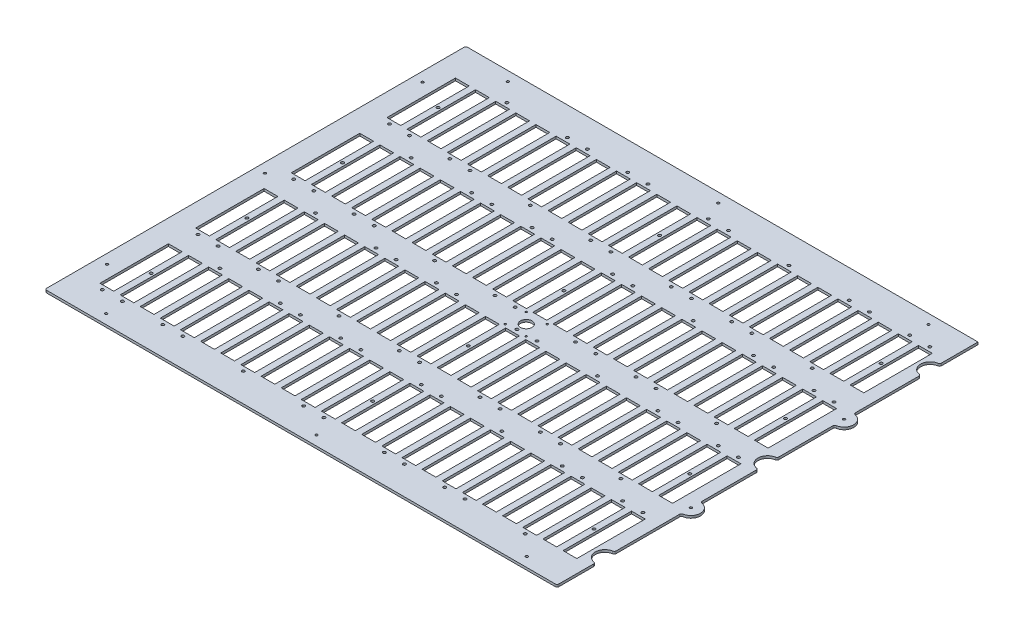
SolidWorks part; units mm, degrees
ref_plane "Front Plane" through (0, 0, 0) normal (0, 0, 1) x (1, 0, 0)
ref_plane "Top Plane" through (0, 0, 0) normal (0, 1, 0) x (1, 0, 0)
ref_plane "Right Plane" through (0, 0, 0) normal (1, 0, 0) x (0, 0, -1)
sketch "Sketch1" plane through (0, 0, 0) normal (0, 1, 0) x (1, 0, 0)
  line L0 (-340.1822, 0) -> (340.1822, 0) construction
  line L1 (-340.1822, -279.5524) -> (340.1822, -279.5524)
  line L2 (-340.1822, -279.5524) -> (-340.1822, 279.5524)
  line L3 (-340.1822, 279.5524) -> (340.1822, 279.5524)
  line L4 (340.1822, -279.5524) -> (340.1822, -228.7524)
  line L5 (-340.1822, -279.5524) -> (340.1822, 279.5524) construction
  line L6 (-340.1822, 279.5524) -> (340.1822, -279.5524) construction
  line L7 (340.1822, -89.0524) -> (340.1822, -12.7)
  line L8 (340.1822, -203.3524) -> (340.1822, -114.4524)
  line L9 (340.1822, 12.7) -> (340.1822, 89.0524)
  line L10 (340.1822, 114.4524) -> (340.1822, 203.3524)
  line L11 (340.1822, 228.7524) -> (340.1822, 279.5524)
  arc A0 (340.1822, 12.7) -> (340.1822, -12.7) centre (340.1822, 0) ccw
  arc A1 (340.1822, -114.4524) -> (340.1822, -89.0524) centre (340.1822, -101.7524) ccw
  arc A2 (340.1822, 89.0524) -> (340.1822, 114.4524) centre (340.1822, 101.7524) ccw
  arc A3 (340.1822, -203.3524) -> (340.1822, -228.7524) centre (340.1822, -216.0524) ccw
  arc A4 (340.1822, 228.7524) -> (340.1822, 203.3524) centre (340.1822, 216.0524) ccw
  point P0 (0, 0)
  dimension "D3" = 63.5
  dimension "D4" = 12.7
  dimension "D5" = 63.5
  dimension "D6" = 177.8
  dimension "D7" = 177.8
  dimension "D1" = 559.1048
  dimension "D2" = 680.3644
extrude "Boss-Extrude1" add sketch "Sketch1" along normal blind 3.175
sketch "Sketch17" plane through (0, 3.175, 0) normal (0, 1, 0) x (1, 0, 0)
  line L0 (340.1822, 279.5524) -> (-340.1822, 279.5524) construction
  line L1 (-314.7822, 254.1524) -> (327.4822, 254.1524) construction
  line L2 (-314.7822, 254.1524) -> (-314.7822, -254.1524) construction
  line L3 (-314.7822, -254.1524) -> (327.4822, -254.1524) construction
  line L4 (327.4822, 254.1524) -> (327.4822, -254.1524) construction
  line L5 (-340.1822, 279.5524) -> (-340.1822, -279.5524) construction
  line L6 (-340.1822, -279.5524) -> (340.1822, -279.5524) construction
  line L7 (340.1822, -203.3524) -> (340.1822, -114.4524) construction
  line L8 (-283.771, 236.1184) -> (-265.483, 236.1184)
  line L9 (-310.515, 236.1184) -> (-292.227, 236.1184)
  line L10 (-310.515, 236.1184) -> (-310.515, 145.1864)
  line L11 (-310.515, 145.1864) -> (-292.227, 145.1864)
  line L12 (-292.227, 236.1184) -> (-292.227, 145.1864)
  line L13 (-283.771, 236.1184) -> (-283.771, 145.1864)
  line L14 (-265.483, 236.1184) -> (-265.483, 145.1864)
  line L15 (-283.771, 145.1864) -> (-265.483, 145.1864)
  line L16 (-257.027, 236.1184) -> (-238.739, 236.1184)
  line L17 (-257.027, 236.1184) -> (-257.027, 145.1864)
  line L18 (-238.739, 236.1184) -> (-238.739, 145.1864)
  line L19 (-257.027, 145.1864) -> (-238.739, 145.1864)
  line L20 (-230.283, 236.1184) -> (-211.995, 236.1184)
  line L21 (-230.283, 236.1184) -> (-230.283, 145.1864)
  line L22 (-211.995, 236.1184) -> (-211.995, 145.1864)
  line L23 (-230.283, 145.1864) -> (-211.995, 145.1864)
  line L24 (-203.539, 236.1184) -> (-185.251, 236.1184)
  line L25 (-203.539, 236.1184) -> (-203.539, 145.1864)
  line L26 (-185.251, 236.1184) -> (-185.251, 145.1864)
  line L27 (-203.539, 145.1864) -> (-185.251, 145.1864)
  line L28 (-176.795, 236.1184) -> (-158.507, 236.1184)
  line L29 (-176.795, 236.1184) -> (-176.795, 145.1864)
  line L30 (-158.507, 236.1184) -> (-158.507, 145.1864)
  line L31 (-176.795, 145.1864) -> (-158.507, 145.1864)
  line L32 (-150.0511, 236.1184) -> (-131.7631, 236.1184)
  line L33 (-150.0511, 236.1184) -> (-150.0511, 145.1864)
  line L34 (-131.7631, 236.1184) -> (-131.7631, 145.1864)
  line L35 (-150.0511, 145.1864) -> (-131.7631, 145.1864)
  line L36 (-123.3071, 236.1184) -> (-105.0191, 236.1184)
  line L37 (-123.3071, 236.1184) -> (-123.3071, 145.1864)
  line L38 (-105.0191, 236.1184) -> (-105.0191, 145.1864)
  line L39 (-123.3071, 145.1864) -> (-105.0191, 145.1864)
  line L40 (-96.5631, 236.1184) -> (-78.2751, 236.1184)
  line L41 (-96.5631, 236.1184) -> (-96.5631, 145.1864)
  line L42 (-78.2751, 236.1184) -> (-78.2751, 145.1864)
  line L43 (-96.5631, 145.1864) -> (-78.2751, 145.1864)
  line L44 (-69.8191, 236.1184) -> (-51.5311, 236.1184)
  line L45 (-69.8191, 236.1184) -> (-69.8191, 145.1864)
  line L46 (-51.5311, 236.1184) -> (-51.5311, 145.1864)
  line L47 (-69.8191, 145.1864) -> (-51.5311, 145.1864)
  line L48 (-43.0751, 236.1184) -> (-24.7871, 236.1184)
  line L49 (-43.0751, 236.1184) -> (-43.0751, 145.1864)
  line L50 (-24.7871, 236.1184) -> (-24.7871, 145.1864)
  line L51 (-43.0751, 145.1864) -> (-24.7871, 145.1864)
  line L52 (-16.3311, 236.1184) -> (1.9569, 236.1184)
  line L53 (-16.3311, 236.1184) -> (-16.3311, 145.1864)
  line L54 (1.9569, 236.1184) -> (1.9569, 145.1864)
  line L55 (-16.3311, 145.1864) -> (1.9569, 145.1864)
  line L56 (10.4129, 236.1184) -> (28.7009, 236.1184)
  line L57 (10.4129, 236.1184) -> (10.4129, 145.1864)
  line L58 (28.7009, 236.1184) -> (28.7009, 145.1864)
  line L59 (10.4129, 145.1864) -> (28.7009, 145.1864)
  line L60 (37.1569, 236.1184) -> (55.4449, 236.1184)
  line L61 (37.1569, 236.1184) -> (37.1569, 145.1864)
  line L62 (55.4449, 236.1184) -> (55.4449, 145.1864)
  line L63 (37.1569, 145.1864) -> (55.4449, 145.1864)
  line L64 (63.9009, 236.1184) -> (82.1889, 236.1184)
  line L65 (63.9009, 236.1184) -> (63.9009, 145.1864)
  line L66 (82.1889, 236.1184) -> (82.1889, 145.1864)
  line L67 (63.9009, 145.1864) -> (82.1889, 145.1864)
  line L68 (90.6449, 236.1184) -> (108.9329, 236.1184)
  line L69 (90.6449, 236.1184) -> (90.6449, 145.1864)
  line L70 (108.9329, 236.1184) -> (108.9329, 145.1864)
  line L71 (90.6449, 145.1864) -> (108.9329, 145.1864)
  line L72 (117.3889, 236.1184) -> (135.6769, 236.1184)
  line L73 (117.3889, 236.1184) -> (117.3889, 145.1864)
  line L74 (135.6769, 236.1184) -> (135.6769, 145.1864)
  line L75 (117.3889, 145.1864) -> (135.6769, 145.1864)
  line L76 (144.1329, 236.1184) -> (162.4209, 236.1184)
  line L77 (144.1329, 236.1184) -> (144.1329, 145.1864)
  line L78 (162.4209, 236.1184) -> (162.4209, 145.1864)
  line L79 (144.1329, 145.1864) -> (162.4209, 145.1864)
  line L80 (170.8768, 236.1184) -> (189.1648, 236.1184)
  line L81 (170.8768, 236.1184) -> (170.8768, 145.1864)
  line L82 (189.1648, 236.1184) -> (189.1648, 145.1864)
  line L83 (170.8768, 145.1864) -> (189.1648, 145.1864)
  line L84 (197.6208, 236.1184) -> (215.9088, 236.1184)
  line L85 (197.6208, 236.1184) -> (197.6208, 145.1864)
  line L86 (215.9088, 236.1184) -> (215.9088, 145.1864)
  line L87 (197.6208, 145.1864) -> (215.9088, 145.1864)
  line L88 (224.3648, 236.1184) -> (242.6528, 236.1184)
  line L89 (224.3648, 236.1184) -> (224.3648, 145.1864)
  line L90 (242.6528, 236.1184) -> (242.6528, 145.1864)
  line L91 (224.3648, 145.1864) -> (242.6528, 145.1864)
  line L92 (251.1088, 236.1184) -> (269.3968, 236.1184)
  line L93 (251.1088, 236.1184) -> (251.1088, 145.1864)
  line L94 (269.3968, 236.1184) -> (269.3968, 145.1864)
  line L95 (251.1088, 145.1864) -> (269.3968, 145.1864)
  line L96 (277.8528, 236.1184) -> (296.1408, 236.1184)
  line L97 (277.8528, 236.1184) -> (277.8528, 145.1864)
  line L98 (296.1408, 236.1184) -> (296.1408, 145.1864)
  line L99 (277.8528, 145.1864) -> (296.1408, 145.1864)
  line L100 (304.5968, 236.1184) -> (322.8848, 236.1184)
  line L101 (304.5968, 236.1184) -> (304.5968, 145.1864)
  line L102 (322.8848, 236.1184) -> (322.8848, 145.1864)
  line L103 (304.5968, 145.1864) -> (322.8848, 145.1864)
  line L104 (-283.771, 109.0422) -> (-265.483, 109.0422)
  line L105 (-283.771, 109.0422) -> (-283.771, 18.1102)
  line L106 (-265.483, 109.0422) -> (-265.483, 18.1102)
  line L107 (-283.771, 18.1102) -> (-265.483, 18.1102)
  line L108 (-257.027, 109.0422) -> (-238.739, 109.0422)
  line L109 (-257.027, 109.0422) -> (-257.027, 18.1102)
  line L110 (-238.739, 109.0422) -> (-238.739, 18.1102)
  line L111 (-257.027, 18.1102) -> (-238.739, 18.1102)
  line L112 (-230.283, 109.0422) -> (-211.995, 109.0422)
  line L113 (-230.283, 109.0422) -> (-230.283, 18.1102)
  line L114 (-211.995, 109.0422) -> (-211.995, 18.1102)
  line L115 (-230.283, 18.1102) -> (-211.995, 18.1102)
  line L116 (-203.539, 109.0422) -> (-185.251, 109.0422)
  line L117 (-203.539, 109.0422) -> (-203.539, 18.1102)
  line L118 (-185.251, 109.0422) -> (-185.251, 18.1102)
  line L119 (-203.539, 18.1102) -> (-185.251, 18.1102)
  line L120 (-176.795, 109.0422) -> (-158.507, 109.0422)
  line L121 (-176.795, 109.0422) -> (-176.795, 18.1102)
  line L122 (-158.507, 109.0422) -> (-158.507, 18.1102)
  line L123 (-176.795, 18.1102) -> (-158.507, 18.1102)
  line L124 (-150.0511, 109.0422) -> (-131.7631, 109.0422)
  line L125 (-150.0511, 109.0422) -> (-150.0511, 18.1102)
  line L126 (-131.7631, 109.0422) -> (-131.7631, 18.1102)
  line L127 (-150.0511, 18.1102) -> (-131.7631, 18.1102)
  line L128 (-123.3071, 109.0422) -> (-105.0191, 109.0422)
  line L129 (-123.3071, 109.0422) -> (-123.3071, 18.1102)
  line L130 (-105.0191, 109.0422) -> (-105.0191, 18.1102)
  line L131 (-123.3071, 18.1102) -> (-105.0191, 18.1102)
  line L132 (-96.5631, 109.0422) -> (-78.2751, 109.0422)
  line L133 (-96.5631, 109.0422) -> (-96.5631, 18.1102)
  line L134 (-78.2751, 109.0422) -> (-78.2751, 18.1102)
  line L135 (-96.5631, 18.1102) -> (-78.2751, 18.1102)
  line L136 (-69.8191, 109.0422) -> (-51.5311, 109.0422)
  line L137 (-69.8191, 109.0422) -> (-69.8191, 18.1102)
  line L138 (-51.5311, 109.0422) -> (-51.5311, 18.1102)
  line L139 (-69.8191, 18.1102) -> (-51.5311, 18.1102)
  line L140 (-43.0751, 109.0422) -> (-24.7871, 109.0422)
  line L141 (-43.0751, 109.0422) -> (-43.0751, 18.1102)
  line L142 (-24.7871, 109.0422) -> (-24.7871, 18.1102)
  line L143 (-43.0751, 18.1102) -> (-24.7871, 18.1102)
  line L144 (-16.3311, 109.0422) -> (1.9569, 109.0422)
  line L145 (-16.3311, 109.0422) -> (-16.3311, 18.1102)
  line L146 (1.9569, 109.0422) -> (1.9569, 18.1102)
  line L147 (-16.3311, 18.1102) -> (1.9569, 18.1102)
  line L148 (10.4129, 109.0422) -> (28.7009, 109.0422)
  line L149 (10.4129, 109.0422) -> (10.4129, 18.1102)
  line L150 (28.7009, 109.0422) -> (28.7009, 18.1102)
  line L151 (10.4129, 18.1102) -> (28.7009, 18.1102)
  line L152 (37.1569, 109.0422) -> (55.4449, 109.0422)
  line L153 (37.1569, 109.0422) -> (37.1569, 18.1102)
  line L154 (55.4449, 109.0422) -> (55.4449, 18.1102)
  line L155 (37.1569, 18.1102) -> (55.4449, 18.1102)
  line L156 (63.9009, 109.0422) -> (82.1889, 109.0422)
  line L157 (63.9009, 109.0422) -> (63.9009, 18.1102)
  line L158 (82.1889, 109.0422) -> (82.1889, 18.1102)
  line L159 (63.9009, 18.1102) -> (82.1889, 18.1102)
  line L160 (90.6449, 109.0422) -> (108.9329, 109.0422)
  line L161 (90.6449, 109.0422) -> (90.6449, 18.1102)
  line L162 (108.9329, 109.0422) -> (108.9329, 18.1102)
  line L163 (90.6449, 18.1102) -> (108.9329, 18.1102)
  line L164 (117.3889, 109.0422) -> (135.6769, 109.0422)
  line L165 (117.3889, 109.0422) -> (117.3889, 18.1102)
  line L166 (135.6769, 109.0422) -> (135.6769, 18.1102)
  line L167 (117.3889, 18.1102) -> (135.6769, 18.1102)
  line L168 (144.1329, 109.0422) -> (162.4209, 109.0422)
  line L169 (144.1329, 109.0422) -> (144.1329, 18.1102)
  line L170 (162.4209, 109.0422) -> (162.4209, 18.1102)
  line L171 (144.1329, 18.1102) -> (162.4209, 18.1102)
  line L172 (170.8768, 109.0422) -> (189.1648, 109.0422)
  line L173 (170.8768, 109.0422) -> (170.8768, 18.1102)
  line L174 (189.1648, 109.0422) -> (189.1648, 18.1102)
  line L175 (170.8768, 18.1102) -> (189.1648, 18.1102)
  line L176 (197.6208, 109.0422) -> (215.9088, 109.0422)
  line L177 (197.6208, 109.0422) -> (197.6208, 18.1102)
  line L178 (215.9088, 109.0422) -> (215.9088, 18.1102)
  line L179 (197.6208, 18.1102) -> (215.9088, 18.1102)
  line L180 (224.3648, 109.0422) -> (242.6528, 109.0422)
  line L181 (224.3648, 109.0422) -> (224.3648, 18.1102)
  line L182 (242.6528, 109.0422) -> (242.6528, 18.1102)
  line L183 (224.3648, 18.1102) -> (242.6528, 18.1102)
  line L184 (251.1088, 109.0422) -> (269.3968, 109.0422)
  line L185 (251.1088, 109.0422) -> (251.1088, 18.1102)
  line L186 (269.3968, 109.0422) -> (269.3968, 18.1102)
  line L187 (251.1088, 18.1102) -> (269.3968, 18.1102)
  line L188 (277.8528, 109.0422) -> (296.1408, 109.0422)
  line L189 (277.8528, 109.0422) -> (277.8528, 18.1102)
  line L190 (296.1408, 109.0422) -> (296.1408, 18.1102)
  line L191 (277.8528, 18.1102) -> (296.1408, 18.1102)
  line L192 (304.5968, 109.0422) -> (322.8848, 109.0422)
  line L193 (304.5968, 109.0422) -> (304.5968, 18.1102)
  line L194 (322.8848, 109.0422) -> (322.8848, 18.1102)
  line L195 (304.5968, 18.1102) -> (322.8848, 18.1102)
  line L196 (-283.771, -18.034) -> (-265.483, -18.034)
  line L197 (-283.771, -18.034) -> (-283.771, -108.966)
  line L198 (-265.483, -18.034) -> (-265.483, -108.966)
  line L199 (-283.771, -108.966) -> (-265.483, -108.966)
  line L200 (-257.027, -18.034) -> (-238.739, -18.034)
  line L201 (-257.027, -18.034) -> (-257.027, -108.966)
  line L202 (-238.739, -18.034) -> (-238.739, -108.966)
  line L203 (-257.027, -108.966) -> (-238.739, -108.966)
  line L204 (-230.283, -18.034) -> (-211.995, -18.034)
  line L205 (-230.283, -18.034) -> (-230.283, -108.966)
  line L206 (-211.995, -18.034) -> (-211.995, -108.966)
  line L207 (-230.283, -108.966) -> (-211.995, -108.966)
  line L208 (-203.539, -18.034) -> (-185.251, -18.034)
  line L209 (-203.539, -18.034) -> (-203.539, -108.966)
  line L210 (-185.251, -18.034) -> (-185.251, -108.966)
  line L211 (-203.539, -108.966) -> (-185.251, -108.966)
  line L212 (-176.795, -18.034) -> (-158.507, -18.034)
  line L213 (-176.795, -18.034) -> (-176.795, -108.966)
  line L214 (-158.507, -18.034) -> (-158.507, -108.966)
  line L215 (-176.795, -108.966) -> (-158.507, -108.966)
  line L216 (-150.0511, -18.034) -> (-131.7631, -18.034)
  line L217 (-150.0511, -18.034) -> (-150.0511, -108.966)
  line L218 (-131.7631, -18.034) -> (-131.7631, -108.966)
  line L219 (-150.0511, -108.966) -> (-131.7631, -108.966)
  line L220 (-123.3071, -18.034) -> (-105.0191, -18.034)
  line L221 (-123.3071, -18.034) -> (-123.3071, -108.966)
  line L222 (-105.0191, -18.034) -> (-105.0191, -108.966)
  line L223 (-123.3071, -108.966) -> (-105.0191, -108.966)
  line L224 (-96.5631, -18.034) -> (-78.2751, -18.034)
  line L225 (-96.5631, -18.034) -> (-96.5631, -108.966)
  line L226 (-78.2751, -18.034) -> (-78.2751, -108.966)
  line L227 (-96.5631, -108.966) -> (-78.2751, -108.966)
  line L228 (-69.8191, -18.034) -> (-51.5311, -18.034)
  line L229 (-69.8191, -18.034) -> (-69.8191, -108.966)
  line L230 (-51.5311, -18.034) -> (-51.5311, -108.966)
  line L231 (-69.8191, -108.966) -> (-51.5311, -108.966)
  line L232 (-43.0751, -18.034) -> (-24.7871, -18.034)
  line L233 (-43.0751, -18.034) -> (-43.0751, -108.966)
  line L234 (-24.7871, -18.034) -> (-24.7871, -108.966)
  line L235 (-43.0751, -108.966) -> (-24.7871, -108.966)
  line L236 (-16.3311, -18.034) -> (1.9569, -18.034)
  line L237 (-16.3311, -18.034) -> (-16.3311, -108.966)
  line L238 (1.9569, -18.034) -> (1.9569, -108.966)
  line L239 (-16.3311, -108.966) -> (1.9569, -108.966)
  line L240 (10.4129, -18.034) -> (28.7009, -18.034)
  line L241 (10.4129, -18.034) -> (10.4129, -108.966)
  line L242 (28.7009, -18.034) -> (28.7009, -108.966)
  line L243 (10.4129, -108.966) -> (28.7009, -108.966)
  line L244 (37.1569, -18.034) -> (55.4449, -18.034)
  line L245 (37.1569, -18.034) -> (37.1569, -108.966)
  line L246 (55.4449, -18.034) -> (55.4449, -108.966)
  line L247 (37.1569, -108.966) -> (55.4449, -108.966)
  line L248 (63.9009, -18.034) -> (82.1889, -18.034)
  line L249 (63.9009, -18.034) -> (63.9009, -108.966)
  line L250 (82.1889, -18.034) -> (82.1889, -108.966)
  line L251 (63.9009, -108.966) -> (82.1889, -108.966)
  line L252 (90.6449, -18.034) -> (108.9329, -18.034)
  line L253 (90.6449, -18.034) -> (90.6449, -108.966)
  line L254 (108.9329, -18.034) -> (108.9329, -108.966)
  line L255 (90.6449, -108.966) -> (108.9329, -108.966)
  line L256 (117.3889, -18.034) -> (135.6769, -18.034)
  line L257 (117.3889, -18.034) -> (117.3889, -108.966)
  line L258 (135.6769, -18.034) -> (135.6769, -108.966)
  line L259 (117.3889, -108.966) -> (135.6769, -108.966)
  line L260 (144.1329, -18.034) -> (162.4209, -18.034)
  line L261 (144.1329, -18.034) -> (144.1329, -108.966)
  line L262 (162.4209, -18.034) -> (162.4209, -108.966)
  line L263 (144.1329, -108.966) -> (162.4209, -108.966)
  line L264 (170.8768, -18.034) -> (189.1648, -18.034)
  line L265 (170.8768, -18.034) -> (170.8768, -108.966)
  line L266 (189.1648, -18.034) -> (189.1648, -108.966)
  line L267 (170.8768, -108.966) -> (189.1648, -108.966)
  line L268 (197.6208, -18.034) -> (215.9088, -18.034)
  line L269 (197.6208, -18.034) -> (197.6208, -108.966)
  line L270 (215.9088, -18.034) -> (215.9088, -108.966)
  line L271 (197.6208, -108.966) -> (215.9088, -108.966)
  line L272 (224.3648, -18.034) -> (242.6528, -18.034)
  line L273 (224.3648, -18.034) -> (224.3648, -108.966)
  line L274 (242.6528, -18.034) -> (242.6528, -108.966)
  line L275 (224.3648, -108.966) -> (242.6528, -108.966)
  line L276 (251.1088, -18.034) -> (269.3968, -18.034)
  line L277 (251.1088, -18.034) -> (251.1088, -108.966)
  line L278 (269.3968, -18.034) -> (269.3968, -108.966)
  line L279 (251.1088, -108.966) -> (269.3968, -108.966)
  line L280 (277.8528, -18.034) -> (296.1408, -18.034)
  line L281 (277.8528, -18.034) -> (277.8528, -108.966)
  line L282 (296.1408, -18.034) -> (296.1408, -108.966)
  line L283 (277.8528, -108.966) -> (296.1408, -108.966)
  line L284 (304.5968, -18.034) -> (322.8848, -18.034)
  line L285 (304.5968, -18.034) -> (304.5968, -108.966)
  line L286 (322.8848, -18.034) -> (322.8848, -108.966)
  line L287 (304.5968, -108.966) -> (322.8848, -108.966)
  line L288 (-283.771, -145.1102) -> (-265.483, -145.1102)
  line L289 (-283.771, -145.1102) -> (-283.771, -236.0422)
  line L290 (-265.483, -145.1102) -> (-265.483, -236.0422)
  line L291 (-283.771, -236.0422) -> (-265.483, -236.0422)
  line L292 (-257.027, -145.1102) -> (-238.739, -145.1102)
  line L293 (-257.027, -145.1102) -> (-257.027, -236.0422)
  line L294 (-238.739, -145.1102) -> (-238.739, -236.0422)
  line L295 (-257.027, -236.0422) -> (-238.739, -236.0422)
  line L296 (-230.283, -145.1102) -> (-211.995, -145.1102)
  line L297 (-230.283, -145.1102) -> (-230.283, -236.0422)
  line L298 (-211.995, -145.1102) -> (-211.995, -236.0422)
  line L299 (-230.283, -236.0422) -> (-211.995, -236.0422)
  line L300 (-203.539, -145.1102) -> (-185.251, -145.1102)
  line L301 (-203.539, -145.1102) -> (-203.539, -236.0422)
  line L302 (-185.251, -145.1102) -> (-185.251, -236.0422)
  line L303 (-203.539, -236.0422) -> (-185.251, -236.0422)
  line L304 (-176.795, -145.1102) -> (-158.507, -145.1102)
  line L305 (-176.795, -145.1102) -> (-176.795, -236.0422)
  line L306 (-158.507, -145.1102) -> (-158.507, -236.0422)
  line L307 (-176.795, -236.0422) -> (-158.507, -236.0422)
  line L308 (-150.0511, -145.1102) -> (-131.7631, -145.1102)
  line L309 (-150.0511, -145.1102) -> (-150.0511, -236.0422)
  line L310 (-131.7631, -145.1102) -> (-131.7631, -236.0422)
  line L311 (-150.0511, -236.0422) -> (-131.7631, -236.0422)
  line L312 (-123.3071, -145.1102) -> (-105.0191, -145.1102)
  line L313 (-123.3071, -145.1102) -> (-123.3071, -236.0422)
  line L314 (-105.0191, -145.1102) -> (-105.0191, -236.0422)
  line L315 (-123.3071, -236.0422) -> (-105.0191, -236.0422)
  line L316 (-96.5631, -145.1102) -> (-78.2751, -145.1102)
  line L317 (-96.5631, -145.1102) -> (-96.5631, -236.0422)
  line L318 (-78.2751, -145.1102) -> (-78.2751, -236.0422)
  line L319 (-96.5631, -236.0422) -> (-78.2751, -236.0422)
  line L320 (-69.8191, -145.1102) -> (-51.5311, -145.1102)
  line L321 (-69.8191, -145.1102) -> (-69.8191, -236.0422)
  line L322 (-51.5311, -145.1102) -> (-51.5311, -236.0422)
  line L323 (-69.8191, -236.0422) -> (-51.5311, -236.0422)
  line L324 (-43.0751, -145.1102) -> (-24.7871, -145.1102)
  line L325 (-43.0751, -145.1102) -> (-43.0751, -236.0422)
  line L326 (-24.7871, -145.1102) -> (-24.7871, -236.0422)
  line L327 (-43.0751, -236.0422) -> (-24.7871, -236.0422)
  line L328 (-16.3311, -145.1102) -> (1.9569, -145.1102)
  line L329 (-16.3311, -145.1102) -> (-16.3311, -236.0422)
  line L330 (1.9569, -145.1102) -> (1.9569, -236.0422)
  line L331 (-16.3311, -236.0422) -> (1.9569, -236.0422)
  line L332 (10.4129, -145.1102) -> (28.7009, -145.1102)
  line L333 (10.4129, -145.1102) -> (10.4129, -236.0422)
  line L334 (28.7009, -145.1102) -> (28.7009, -236.0422)
  line L335 (10.4129, -236.0422) -> (28.7009, -236.0422)
  line L336 (37.1569, -145.1102) -> (55.4449, -145.1102)
  line L337 (37.1569, -145.1102) -> (37.1569, -236.0422)
  line L338 (55.4449, -145.1102) -> (55.4449, -236.0422)
  line L339 (37.1569, -236.0422) -> (55.4449, -236.0422)
  line L340 (63.9009, -145.1102) -> (82.1889, -145.1102)
  line L341 (63.9009, -145.1102) -> (63.9009, -236.0422)
  line L342 (82.1889, -145.1102) -> (82.1889, -236.0422)
  line L343 (63.9009, -236.0422) -> (82.1889, -236.0422)
  line L344 (90.6449, -145.1102) -> (108.9329, -145.1102)
  line L345 (90.6449, -145.1102) -> (90.6449, -236.0422)
  line L346 (108.9329, -145.1102) -> (108.9329, -236.0422)
  line L347 (90.6449, -236.0422) -> (108.9329, -236.0422)
  line L348 (117.3889, -145.1102) -> (135.6769, -145.1102)
  line L349 (117.3889, -145.1102) -> (117.3889, -236.0422)
  line L350 (135.6769, -145.1102) -> (135.6769, -236.0422)
  line L351 (117.3889, -236.0422) -> (135.6769, -236.0422)
  line L352 (144.1329, -145.1102) -> (162.4209, -145.1102)
  line L353 (144.1329, -145.1102) -> (144.1329, -236.0422)
  line L354 (162.4209, -145.1102) -> (162.4209, -236.0422)
  line L355 (144.1329, -236.0422) -> (162.4209, -236.0422)
  line L356 (170.8768, -145.1102) -> (189.1648, -145.1102)
  line L357 (170.8768, -145.1102) -> (170.8768, -236.0422)
  line L358 (189.1648, -145.1102) -> (189.1648, -236.0422)
  line L359 (170.8768, -236.0422) -> (189.1648, -236.0422)
  line L360 (197.6208, -145.1102) -> (215.9088, -145.1102)
  line L361 (197.6208, -145.1102) -> (197.6208, -236.0422)
  line L362 (215.9088, -145.1102) -> (215.9088, -236.0422)
  line L363 (197.6208, -236.0422) -> (215.9088, -236.0422)
  line L364 (224.3648, -145.1102) -> (242.6528, -145.1102)
  line L365 (224.3648, -145.1102) -> (224.3648, -236.0422)
  line L366 (242.6528, -145.1102) -> (242.6528, -236.0422)
  line L367 (224.3648, -236.0422) -> (242.6528, -236.0422)
  line L368 (251.1088, -145.1102) -> (269.3968, -145.1102)
  line L369 (251.1088, -145.1102) -> (251.1088, -236.0422)
  line L370 (269.3968, -145.1102) -> (269.3968, -236.0422)
  line L371 (251.1088, -236.0422) -> (269.3968, -236.0422)
  line L372 (277.8528, -145.1102) -> (296.1408, -145.1102)
  line L373 (277.8528, -145.1102) -> (277.8528, -236.0422)
  line L374 (296.1408, -145.1102) -> (296.1408, -236.0422)
  line L375 (277.8528, -236.0422) -> (296.1408, -236.0422)
  line L376 (304.5968, -145.1102) -> (322.8848, -145.1102)
  line L377 (304.5968, -145.1102) -> (304.5968, -236.0422)
  line L378 (322.8848, -145.1102) -> (322.8848, -236.0422)
  line L379 (304.5968, -236.0422) -> (322.8848, -236.0422)
  line L380 (-310.515, 109.0422) -> (-292.227, 109.0422)
  line L381 (-310.515, 109.0422) -> (-310.515, 18.1102)
  line L382 (-292.227, 109.0422) -> (-292.227, 18.1102)
  line L383 (-310.515, 18.1102) -> (-292.227, 18.1102)
  line L384 (-310.515, -18.034) -> (-292.227, -18.034)
  line L385 (-310.515, -18.034) -> (-310.515, -108.966)
  line L386 (-292.227, -18.034) -> (-292.227, -108.966)
  line L387 (-310.515, -108.966) -> (-292.227, -108.966)
  line L388 (-310.515, -145.1102) -> (-292.227, -145.1102)
  line L389 (-310.515, -145.1102) -> (-310.515, -236.0422)
  line L390 (-292.227, -145.1102) -> (-292.227, -236.0422)
  line L391 (-310.515, -236.0422) -> (-292.227, -236.0422)
  line L392 (340.1822, -279.5524) -> (340.1822, -228.7524) construction
  dimension "D1" = 25.4
  dimension "D2" = 25.4
  dimension "D3" = 25.4
  dimension "D4" = 12.7
  dimension "D5" = 18.288
  dimension "D6" = 90.932
  dimension "D7" = 4.2672
  dimension "D8" = 18.034
  dimension "D9" = 508.3048
  dimension "D10" = 642.2644
  dimension "D11" = 24
  dimension "D13" = 17.2974
  dimension "D14" = 43.5102
  dimension "D12" = 4
extrude "Cut-Extrude5" cut sketch "Sketch17" against normal through all
hole_wizard "#25 (0.1495) Diameter Hole1" positions "Sketch18" profile "Sketch19" hole size "#25" standard "ANSI Inch" end condition through all
sketch "Sketch18" plane through (0, 3.175, 0) normal (0, 1, 0) x (1, 0, 0)
  line L19 (340.1822, -241.8842) -> (-340.1822, -241.8842) construction
  line L20 (340.1822, -279.5524) -> (340.1822, -228.7524) construction
  line L21 (-340.1822, 279.5524) -> (-340.1822, -279.5524) construction
  line L22 (340.1822, -139.2682) -> (-340.1822, -139.2682) construction
  line L23 (340.1822, -203.3524) -> (340.1822, -114.4524) construction
  line L24 (313.7408, -236.0422) -> (313.7408, -254.0762) construction
  line L25 (304.5968, -236.0422) -> (322.8848, -236.0422) construction
  line L29 (322.8848, -145.1102) -> (304.5968, -145.1102) construction
  line L30 (313.7408, -241.8842) -> (313.7408, -139.2682) construction
  line L32 (286.9902, -241.8842) -> (286.9902, -139.2682) construction
  line L33 (260.2396, -241.8842) -> (260.2396, -139.2682) construction
  line L34 (233.4889, -241.8842) -> (233.4889, -139.2682) construction
  line L35 (206.7383, -241.8842) -> (206.7383, -139.2682) construction
  line L36 (179.9877, -241.8842) -> (179.9877, -139.2682) construction
  line L37 (153.2371, -241.8842) -> (153.2371, -139.2682) construction
  line L38 (126.4865, -241.8842) -> (126.4865, -139.2682) construction
  line L39 (99.7359, -241.8842) -> (99.7359, -139.2682) construction
  line L40 (72.9852, -241.8842) -> (72.9852, -139.2682) construction
  line L41 (46.2346, -241.8842) -> (46.2346, -139.2682) construction
  line L42 (19.484, -241.8842) -> (19.484, -139.2682) construction
  line L43 (-7.2666, -241.8842) -> (-7.2666, -139.2682) construction
  line L44 (-34.0172, -241.8842) -> (-34.0172, -139.2682) construction
  line L45 (-60.7678, -241.8842) -> (-60.7678, -139.2682) construction
  line L46 (-87.5185, -241.8842) -> (-87.5185, -139.2682) construction
  line L47 (-114.2691, -241.8842) -> (-114.2691, -139.2682) construction
  line L48 (-141.0197, -241.8842) -> (-141.0197, -139.2682) construction
  line L49 (-167.7703, -241.8842) -> (-167.7703, -139.2682) construction
  line L50 (-194.5209, -241.8842) -> (-194.5209, -139.2682) construction
  line L51 (-221.2715, -241.8842) -> (-221.2715, -139.2682) construction
  line L52 (-248.0222, -241.8842) -> (-248.0222, -139.2682) construction
  line L53 (-274.7728, -241.8842) -> (-274.7728, -139.2682) construction
  line L54 (-301.5234, -241.8842) -> (-301.5234, -139.2682) construction
  point P472 (313.7408, -139.2682)
  point P477 (286.9902, -139.2682)
  point P478 (260.2396, -241.8842)
  point P481 (233.4889, -139.2682)
  point P483 (206.7383, -139.2682)
  point P484 (179.9877, -241.8842)
  point P486 (153.2371, -241.8842)
  point P489 (126.4865, -139.2682)
  point P490 (99.7359, -241.8842)
  point P492 (72.9852, -241.8842)
  point P495 (46.2346, -139.2682)
  point P497 (19.484, -139.2682)
  point P498 (-7.2666, -241.8842)
  point P500 (-34.0172, -241.8842)
  point P503 (-60.7678, -139.2682)
  point P505 (-87.5185, -139.2682)
  point P506 (-114.2691, -241.8842)
  point P509 (-141.0197, -139.2682)
  point P511 (-167.7703, -139.2682)
  point P512 (-194.5209, -241.8842)
  point P514 (-221.2715, -241.8842)
  point P517 (-248.0222, -139.2682)
  point P518 (-274.7728, -241.8842)
  point P520 (-301.5234, -241.8842)
  point P575 (313.7408, -12.192)
  point P576 (286.9902, -12.192)
  point P577 (260.2396, -114.808)
  point P578 (233.4889, -12.192)
  point P579 (206.7383, -12.192)
  point P580 (179.9877, -114.808)
  point P581 (153.2371, -114.808)
  point P582 (126.4865, -12.192)
  point P583 (99.7359, -114.808)
  point P584 (72.9852, -114.808)
  point P585 (46.2346, -12.192)
  point P586 (19.484, -12.192)
  point P587 (-7.2666, -114.808)
  point P588 (-34.0172, -114.808)
  point P589 (-60.7678, -12.192)
  point P590 (-87.5185, -12.192)
  point P591 (-114.2691, -114.808)
  point P592 (-141.0197, -12.192)
  point P593 (-167.7703, -12.192)
  point P594 (-194.5209, -114.808)
  point P595 (-221.2715, -114.808)
  point P596 (-248.0222, -12.192)
  point P597 (-274.7728, -114.808)
  point P598 (-301.5234, -114.808)
  point P599 (313.7408, 114.8842)
  point P600 (286.9902, 114.8842)
  point P601 (260.2396, 12.2682)
  point P602 (233.4889, 114.8842)
  point P603 (206.7383, 114.8842)
  point P604 (179.9877, 12.2682)
  point P605 (153.2371, 12.2682)
  point P606 (126.4865, 114.8842)
  point P607 (99.7359, 12.2682)
  point P608 (72.9852, 12.2682)
  point P609 (46.2346, 114.8842)
  point P610 (19.484, 114.8842)
  point P611 (-7.2666, 12.2682)
  point P612 (-34.0172, 12.2682)
  point P613 (-60.7678, 114.8842)
  point P614 (-87.5185, 114.8842)
  point P615 (-114.2691, 12.2682)
  point P616 (-141.0197, 114.8842)
  point P617 (-167.7703, 114.8842)
  point P618 (-194.5209, 12.2682)
  point P619 (-221.2715, 12.2682)
  point P620 (-248.0222, 114.8842)
  point P621 (-274.7728, 12.2682)
  point P622 (-301.5234, 12.2682)
  point P623 (313.7408, 241.9604)
  point P624 (286.9902, 241.9604)
  point P625 (260.2396, 139.3444)
  point P626 (233.4889, 241.9604)
  point P627 (206.7383, 241.9604)
  point P628 (179.9877, 139.3444)
  point P629 (153.2371, 139.3444)
  point P630 (126.4865, 241.9604)
  point P631 (99.7359, 139.3444)
  point P632 (72.9852, 139.3444)
  point P633 (46.2346, 241.9604)
  point P634 (19.484, 241.9604)
  point P635 (-7.2666, 139.3444)
  point P636 (-34.0172, 139.3444)
  point P637 (-60.7678, 241.9604)
  point P638 (-87.5185, 241.9604)
  point P639 (-114.2691, 139.3444)
  point P640 (-141.0197, 241.9604)
  point P641 (-167.7703, 241.9604)
  point P642 (-194.5209, 139.3444)
  point P643 (-221.2715, 139.3444)
  point P644 (-248.0222, 241.9604)
  point P645 (-274.7728, 139.3444)
  point P646 (-301.5234, 139.3444)
  dimension "D1" = 5.842
  dimension "D2" = 5.842
  dimension "D3" = 24
  dimension "D4" = 4
sketch "Sketch19" plane through (-301.5234, 3.175, -139.3444) normal (1, 0, 0) x (0, 0, 1)
  line L0 (0, 0) -> (0, 3.175)
  line L1 (0, 3.175) -> (1.8986, 3.175)
  line L2 (1.8986, 3.175) -> (1.8986, 0)
  line L5 (1.8986, 0) -> (0, 0)
  line L11 (0, -6.35) -> (0, 107.95) construction
  dimension "Thru Hole Dia." = 3.7973
  dimension "Thru Hole Depth" = 3.175
fillet "Fillet1" radius 2.54 13 edges at (-340.1822, 1.5875, -279.5524) (-340.1822, 1.5875, 279.5524) (340.1822, 1.5875, 279.5524) (340.1822, 1.5875, 203.3524) (340.1822, 1.5875, 228.7524) (340.1822, 1.5875, -228.7524) (340.1822, 1.5875, -203.3524) (340.1822, 1.5875, -114.4524) (340.1822, 1.5875, -89.0524) (340.1822, 1.5875, -12.7) (340.1822, 1.5875, 12.7) (340.1822, 1.5875, 89.0524) (340.1822, 1.5875, 114.4524)
hole_wizard "#6 Clearance Hole1" positions "Sketch8" profile "Sketch9" hole size "#6" standard "ANSI Inch" end condition through all
sketch "Sketch8" plane through (0, 3.175, 0) normal (0, 1, 0) x (1, 0, 0)
  line L13 (-292.227, 236.1184) -> (-283.771, 145.1864) construction
  line L15 (1.9569, 236.1184) -> (10.4129, 145.1864) construction
  line L17 (296.1408, 236.1184) -> (304.5968, 145.1864) construction
  line L18 (-292.227, 109.0422) -> (-283.771, 18.1102) construction
  line L19 (1.9569, 109.0422) -> (10.4129, 18.1102) construction
  line L20 (296.1408, 109.0422) -> (304.5968, 18.1102) construction
  line L21 (-292.227, -18.034) -> (-283.771, -108.966) construction
  line L22 (1.9569, -18.034) -> (10.4129, -108.966) construction
  line L23 (296.1408, -18.034) -> (304.5968, -108.966) construction
  line L24 (-292.227, -145.1102) -> (-283.771, -236.0422) construction
  line L25 (1.9569, -145.1102) -> (10.4129, -236.0422) construction
  line L26 (296.1408, -145.1102) -> (304.5968, -236.0422) construction
  point P129 (-287.999, 190.6524)
  point P131 (6.1849, 190.6524)
  point P133 (300.3688, 190.6524)
  point P146 (-287.999, 63.5762)
  point P147 (6.1849, 63.5762)
  point P148 (300.3688, 63.5762)
  point P155 (-287.999, -63.5)
  point P156 (6.1849, -63.5)
  point P157 (300.3688, -63.5)
  point P164 (-287.999, -190.5762)
  point P165 (6.1849, -190.5762)
  point P166 (300.3688, -190.5762)
  dimension "D1" = 4
sketch "Sketch9" plane through (300.3688, 3.175, 190.5762) normal (1, 0, 0) x (0, 0, 1)
  line L0 (0, 0) -> (0, 3.175)
  line L1 (0, 3.175) -> (1.8986, 3.175)
  line L2 (1.8986, 3.175) -> (1.8986, 0)
  line L5 (1.8986, 0) -> (0, 0)
  line L11 (0, -6.35) -> (0, 107.95) construction
  dimension "Thru Hole Dia." = 3.7973
  dimension "Thru Hole Depth" = 3.175
hole_wizard "#2 Clearance Hole1" positions "Sketch13" profile "Sketch14" hole size "#2" standard "ANSI Inch" end condition through all
sketch "Sketch13" plane through (0, 3.175, 0) normal (0, 1, 0) x (1, 0, 0)
  line L9 (322.8848, -108.966) -> (322.8848, -18.034) construction
  line L10 (322.8848, -18.034) -> (304.5968, -18.034) construction
  line L18 (10.4129, 18.1102) -> (28.7009, -18.034) construction
  line L21 (5.6261, -13.9319) -> (33.5661, -13.9319) construction
  line L22 (5.6261, -13.9319) -> (5.6261, 14.0081) construction
  line L23 (5.6261, 14.0081) -> (33.5661, 14.0081) construction
  line L24 (33.5661, -13.9319) -> (33.5661, 14.0081) construction
  line L25 (5.6261, -13.9319) -> (33.5661, 14.0081) construction
  line L26 (5.6261, 14.0081) -> (33.5661, -13.9319) construction
  line L27 (10.4129, 18.1102) -> (28.7009, 18.1102) construction
  point P129 (5.6261, 14.0081)
  point P132 (5.6261, -13.9319)
  point P135 (33.5661, -13.9319)
  point P138 (33.5661, 14.0081)
  dimension "D1" = 27.94
  dimension "D2" = 27.94
  dimension "D3" = 4.1021
sketch "Sketch14" plane through (33.5661, 3.175, -14.0081) normal (1, 0, 0) x (0, 0, 1)
  line L0 (0, 0) -> (0, 3.175)
  line L1 (0, 3.175) -> (1.2192, 3.175)
  line L2 (1.2192, 3.175) -> (1.2192, 0)
  line L5 (1.2192, 0) -> (0, 0)
  line L11 (0, -6.35) -> (0, 107.95) construction
  dimension "Thru Hole Dia." = 2.4384
  dimension "Thru Hole Depth" = 3.175
sketch "Sketch20" plane through (0, 3.175, 0) normal (0, 1, 0) x (1, 0, 0)
  line L0 (5.6261, 14.0081) -> (33.5661, -13.9319) construction
  circle A0 centre (19.5961, 0.0381) radius 7.62
  dimension "D1" = 15.24
extrude "Cut-Extrude6" cut sketch "Sketch20" against normal through all
hole_wizard "1/8 (0.125) Diameter Hole1" positions "Sketch21" profile "Sketch22" hole size "1/8" standard "ANSI Inch" end condition through all
sketch "Sketch21" plane through (0, 3.175, 0) normal (0, 1, 0) x (1, 0, 0)
  point P0 (287.274, -266.8524)
  point P12 (287.274, 266.8524)
  point P15 (7.874, 266.8524)
  point P18 (-271.526, 266.8524)
  point P21 (-327.5584, 209.55)
  point P24 (-327.5584, 0)
  point P27 (-327.5584, -209.55)
  point P30 (-271.526, -266.8524)
  point P33 (7.874, -266.8524)
  point P56 (340.1822, 101.7524)
  point P59 (340.1822, -101.7524)
sketch "Sketch22" plane through (287.274, 3.175, 266.8524) normal (1, 0, 0) x (0, 0, 1)
  line L0 (0, 0) -> (0, 3.175)
  line L1 (0, 3.175) -> (1.5875, 3.175)
  line L2 (1.5875, 3.175) -> (1.5875, 0)
  line L5 (1.5875, 0) -> (0, 0)
  line L11 (0, -6.35) -> (0, 107.95) construction
  dimension "Thru Hole Dia." = 3.175
  dimension "Thru Hole Depth" = 3.175
